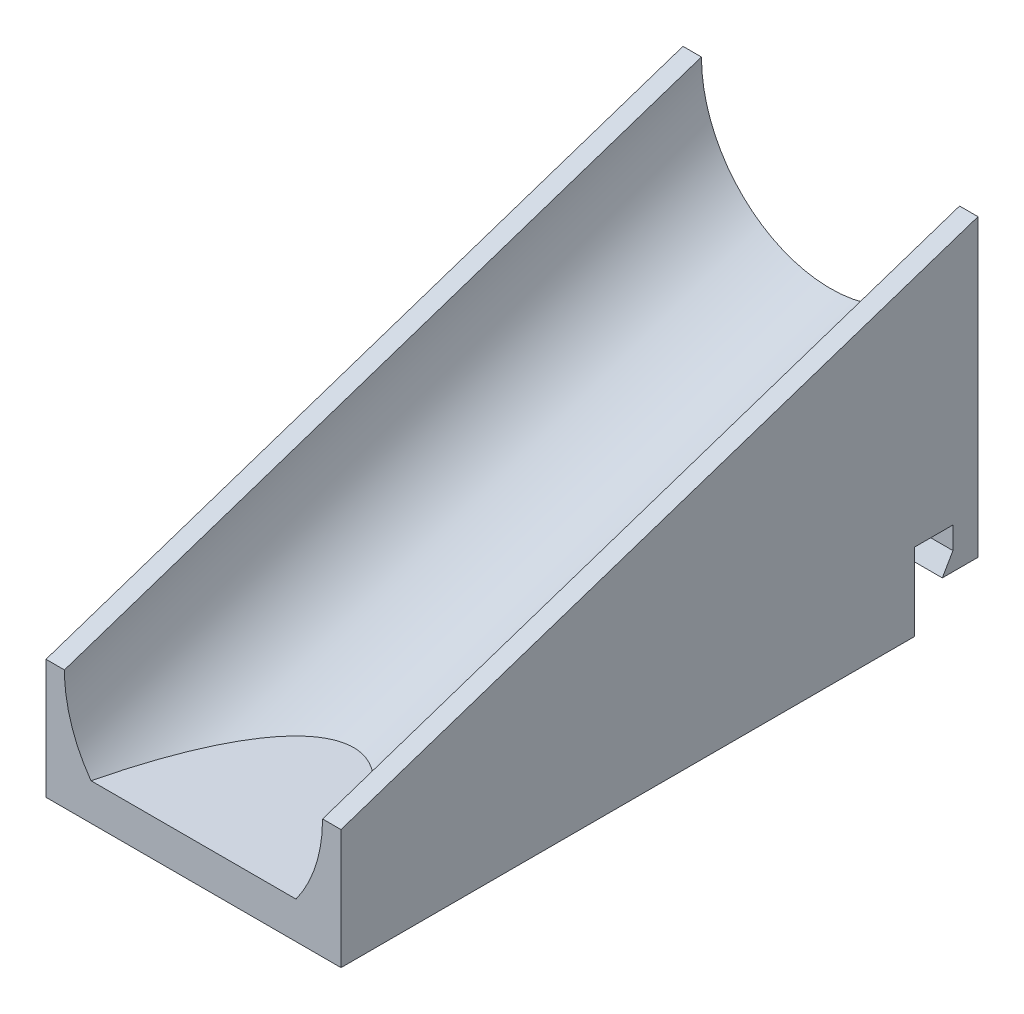
SolidWorks part; units mm, degrees
ref_plane "Front Plane" through (0, 0, 0) normal (0, 0, 1) x (1, 0, 0)
ref_plane "Top Plane" through (0, 0, 0) normal (0, 1, 0) x (1, 0, 0)
ref_plane "Right Plane" through (0, 0, 0) normal (1, 0, 0) x (0, 0, -1)
sketch "Sketch1" plane through (0, 0, 0) normal (0, 1, 0) x (1, 0, 0)
  line L1 (0, 0) -> (101.6, 0)
  line L2 (0, 0) -> (0, -304.8)
  line L3 (0, -304.8) -> (101.6, -304.8)
  line L4 (101.6, 0) -> (101.6, -304.8)
  dimension "D1" = 101.6
  dimension "D2" = 304.8
extrude "Boss-Extrude1" add sketch "Sketch1" along normal blind 101.6
sketch "Sketch3" plane through (101.6, 0, 0) normal (1, 0, 0) x (0, 0, -1)
  line L0 (-304.8, 0) -> (0, 101.6)
  line L1 (0, 101.6) -> (-304.8, 101.6)
  line L2 (-304.8, 101.6) -> (-304.8, 0)
extrude "Cut-Extrude1" cut sketch "Sketch3" against normal blind 101.6
ref_plane "Plane1" through (0, 10.16, -30.48) normal (0, 0.3162, -0.9487) x (-1, 0, 0)
sketch "Sketch4" plane through (0, 10.16, -30.48) normal (0, 0.3162, -0.9487) x (-1, 0, 0)
  line L0 (-101.6, 96.3862) -> (0, 96.3862) construction
  circle A0 centre (-50.8, 96.3862) radius 44.45
  dimension "D1" = 88.9
extrude "Cut-Extrude2" cut sketch "Sketch4" against normal blind 508
sketch "Sketch7" plane through (101.6, 0, 0) normal (1, 0, 0) x (0, 0, -1)
  line L0 (-304.8, 0) -> (0, 0) construction
  line L1 (-21.79, 0) -> (-8.636, 0)
  line L2 (-21.79, 0) -> (-21.79, 13.97)
  line L3 (-21.79, 13.97) -> (-8.636, 13.97)
  line L4 (-8.636, 0) -> (-8.636, 13.97)
  line L5 (0, 101.6) -> (0, 0) construction
  dimension "D1" = 13.154
  dimension "D2" = 8.636
  dimension "D3" = 13.97
extrude "Cut-Extrude3" cut sketch "Sketch7" against normal blind 152.4
sketch "Sketch8" plane through (0, 0, 8.636) normal (0, 0, 1) x (1, 0, 0)
  line L0 (0, 0) -> (0, 13.97) construction
  line L1 (101.6, 0) -> (0, 0)
  line L2 (101.6, 0) -> (101.6, 6.985)
  line L3 (101.6, 6.985) -> (0, 6.985)
  line L4 (0, 0) -> (0, 6.985)
extrude "Boss-Extrude2" add sketch "Sketch8" along normal blind 6.35
chamfer "Chamfer1" distance 6.731 angle 60 1 edges at (50.8, 6.985, 14.986) first distance on face at (50.8, 6.985, 11.811)
sketch "Sketch9" plane through (0, 0, 0) normal (0, -1, 0) x (1, 0, 0)
  line L0 (101.6, 21.79) -> (0, 21.79)
  line L1 (101.6, 21.79) -> (101.6, 314.6167)
  line L2 (0, 21.79) -> (0, 314.6167)
  line L3 (101.6, 314.6167) -> (0, 314.6167)
  line L4 (0, 21.79) -> (101.6, 21.79) construction
extrude "Boss-Extrude3" add sketch "Sketch9" along normal blind 12.7
sketch "Sketch10" plane through (0, -12.7, 0) normal (0, -1, 0) x (-1, 0, 0)
  line L0 (-101.6, -314.6167) -> (0, -314.6167)
  line L1 (-101.6, -314.6167) -> (-101.6, -219.3667)
  line L2 (0, -314.6167) -> (0, -219.3667)
  line L3 (-101.6, -219.3667) -> (0, -219.3667)
  line L4 (-101.6, -21.79) -> (-101.6, -314.6167) construction
  line L5 (-101.6, -314.6167) -> (0, -314.6167) construction
  line L6 (0, -314.6167) -> (0, -21.79) construction
  dimension "D1" = 95.25
extrude "Cut-Extrude4" cut sketch "Sketch10" against normal blind 58.42
